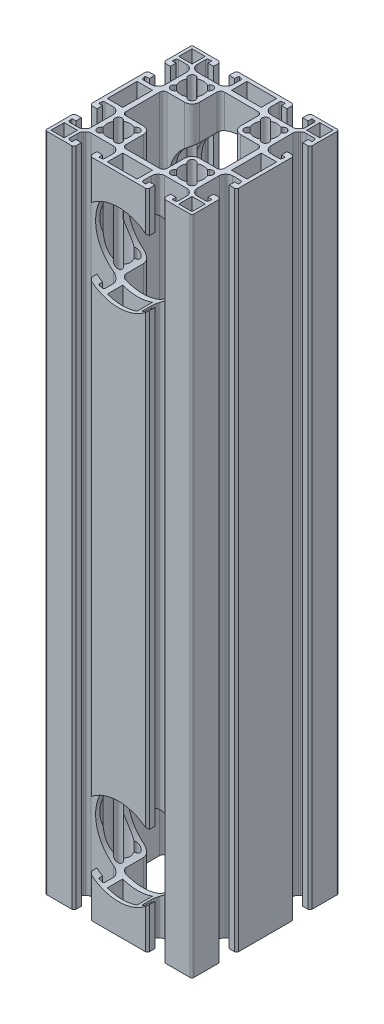
SolidWorks part; units mm, degrees
ref_plane "Front Plane" through (0, 0, 0) normal (0, 0, 1) x (1, 0, 0)
ref_plane "Top Plane" through (0, 0, 0) normal (0, 1, 0) x (1, 0, 0)
ref_plane "Right Plane" through (0, 0, 0) normal (1, 0, 0) x (0, 0, -1)
sketch "Sketch1" plane through (0, 0, 0) normal (0, 1, 0) x (1, 0, 0)
  line L0 (16.5224, 10.1082) -> (17.1083, 10.6941)
  line L2 (14.2799, 13.5226) -> (13.694, 12.9366)
  line L7 (13.694, 19.6541) -> (14.2799, 19.0682)
  line L8 (17.1083, 21.8966) -> (16.5224, 22.4826)
  line L9 (23.2399, 22.4826) -> (22.654, 21.8966)
  line L10 (25.4824, 19.0682) -> (26.0683, 19.6541)
  line L11 (26.0683, 12.9366) -> (25.4824, 13.5226)
  line L12 (22.654, 10.6941) -> (23.2399, 10.1082)
  line L13 (-29.7188, -11.8046) -> (-29.7188, 4.3954)
  line L14 (-38.1188, -11.8046) -> (-29.7188, -11.8046)
  line L15 (-38.1188, 4.3954) -> (-38.1188, -11.8046)
  line L16 (-29.7188, 4.3954) -> (-38.1188, 4.3954)
  line L17 (-23.4776, 10.1082) -> (-22.8917, 10.6941)
  line L18 (-25.7201, 13.5226) -> (-26.306, 12.9366)
  line L19 (-26.306, 19.6541) -> (-25.7201, 19.0682)
  line L20 (-22.8917, 21.8966) -> (-23.4776, 22.4826)
  line L21 (-16.7601, 22.4826) -> (-17.346, 21.8966)
  line L22 (-14.5176, 19.0682) -> (-13.9317, 19.6541)
  line L23 (-13.9317, 12.9366) -> (-14.5176, 13.5226)
  line L24 (-17.346, 10.6941) -> (-16.7601, 10.1082)
  line L26 (23.2399, -17.5174) -> (22.654, -18.1034)
  line L27 (25.4824, -20.9318) -> (26.0683, -20.3459)
  line L28 (26.0683, -27.0634) -> (25.4824, -26.4774)
  line L29 (22.654, -29.3059) -> (23.2399, -29.8918)
  line L30 (16.5224, -29.8918) -> (17.1083, -29.3059)
  line L31 (14.2799, -26.4774) -> (13.694, -27.0634)
  line L32 (13.694, -20.3459) -> (14.2799, -20.9318)
  line L33 (17.1083, -18.1034) -> (16.5224, -17.5174)
  line L41 (-31.3188, -34.9046) -> (-38.5188, -34.9046)
  line L42 (-31.3188, -42.1046) -> (-31.3188, -34.9046)
  line L43 (-38.5188, -42.1046) -> (-31.3188, -42.1046)
  line L44 (-38.5188, -34.9046) -> (-38.5188, -42.1046)
  line L45 (-16.7601, -17.5174) -> (-17.346, -18.1034)
  line L46 (-14.5176, -20.9318) -> (-13.9317, -20.3459)
  line L51 (-13.9317, -27.0634) -> (-14.5176, -26.4774)
  line L52 (-17.346, -29.3059) -> (-16.7601, -29.8918)
  line L53 (-23.4776, -29.8918) -> (-22.8917, -29.3059)
  line L54 (-25.7201, -26.4774) -> (-26.306, -27.0634)
  line L55 (-26.306, -20.3459) -> (-25.7201, -20.9318)
  line L56 (-22.8917, -18.1034) -> (-23.4776, -17.5174)
  line L57 (-38.5188, 27.4954) -> (-31.3188, 27.4954)
  line L58 (-38.5188, 34.6954) -> (-38.5188, 27.4954)
  line L59 (-31.3188, 34.6954) -> (-38.5188, 34.6954)
  line L60 (-31.3188, 27.4954) -> (-31.3188, 34.6954)
  line L61 (38.2812, -34.9046) -> (31.0812, -34.9046)
  line L62 (38.2812, -42.1046) -> (38.2812, -34.9046)
  line L63 (31.0812, -42.1046) -> (38.2812, -42.1046)
  line L64 (31.0812, -34.9046) -> (31.0812, -42.1046)
  line L65 (31.0812, 27.4954) -> (38.2812, 27.4954)
  line L66 (31.0812, 34.6954) -> (31.0812, 27.4954)
  line L67 (38.2812, 34.6954) -> (31.0812, 34.6954)
  line L68 (38.2812, 27.4954) -> (38.2812, 34.6954)
  line L69 (-8.2188, 34.2954) -> (-8.2188, 25.8954)
  line L70 (7.9812, 34.2954) -> (-8.2188, 34.2954)
  line L71 (7.9812, 25.8954) -> (7.9812, 34.2954)
  line L72 (-8.2188, 25.8954) -> (7.9812, 25.8954)
  line L79 (11.0812, -28.5046) -> (11.0812, -18.9046)
  line L80 (-9.3188, -30.5046) -> (9.0812, -30.5046)
  line L81 (-11.3188, -18.9046) -> (-11.3188, -28.5046)
  line L82 (-24.9188, -14.9046) -> (-15.3188, -14.9046)
  line L83 (-26.9188, 5.4954) -> (-26.9188, -12.9046)
  line L84 (-15.3188, 7.4954) -> (-24.9188, 7.4954)
  line L89 (-11.3188, 21.0954) -> (-11.3188, 11.4954)
  line L90 (9.0812, 23.0954) -> (-9.3188, 23.0954)
  line L91 (11.0812, 11.4954) -> (11.0812, 21.0954)
  line L92 (24.6812, 7.4954) -> (15.0812, 7.4954)
  line L93 (26.6812, -12.9046) -> (26.6812, 5.4954)
  line L94 (15.0812, -14.9046) -> (24.6812, -14.9046)
  line L95 (7.9812, -33.3046) -> (-8.2188, -33.3046)
  line L96 (7.9812, -41.7046) -> (7.9812, -33.3046)
  line L97 (-8.2188, -41.7046) -> (7.9812, -41.7046)
  line L98 (-8.2188, -33.3046) -> (-8.2188, -41.7046)
  line L99 (29.4812, 4.3954) -> (29.4812, -11.8046)
  line L100 (37.8812, 4.3954) -> (29.4812, 4.3954)
  line L101 (37.8812, -11.8046) -> (37.8812, 4.3954)
  line L102 (29.4812, -11.8046) -> (37.8812, -11.8046)
  line L103 (39.8812, -42.7046) -> (39.8812, -28.9546)
  line L104 (39.8812, -28.9546) -> (38.8812, -27.9546)
  line L105 (38.8812, -27.9546) -> (35.8812, -27.9546)
  line L106 (35.8812, -27.9546) -> (35.8812, -30.9546)
  line L107 (35.8812, -30.9546) -> (37.4853, -30.9546)
  line L108 (37.9777, -31.5414) -> (37.7979, -32.5609)
  line L109 (36.9116, -33.3046) -> (32.215, -33.3046)
  line L110 (30.0937, -32.4259) -> (29.5598, -31.8921)
  line L111 (28.6812, -29.7708) -> (28.6812, -17.6385)
  line L118 (29.5598, -15.5172) -> (30.0937, -14.9833)
  line L119 (32.215, -14.1046) -> (36.9116, -14.1046)
  line L120 (37.7979, -14.8483) -> (37.9777, -15.8678)
  line L121 (37.4853, -16.4546) -> (35.8812, -16.4546)
  line L122 (35.8812, -16.4546) -> (35.8812, -19.4546)
  line L123 (35.8812, -19.4546) -> (38.8812, -19.4546)
  line L128 (38.8812, -19.4546) -> (39.8812, -18.4546)
  line L129 (39.8812, -18.4546) -> (39.8812, 11.0454)
  line L130 (39.8812, 11.0454) -> (38.8812, 12.0454)
  line L131 (38.8812, 12.0454) -> (35.8812, 12.0454)
  line L132 (35.8812, 12.0454) -> (35.8812, 9.0454)
  line L133 (35.8812, 9.0454) -> (37.4853, 9.0454)
  line L134 (37.9777, 8.4586) -> (37.7979, 7.4391)
  line L135 (36.9116, 6.6954) -> (32.215, 6.6954)
  line L136 (30.0937, 7.5741) -> (29.5598, 8.1079)
  line L137 (28.6812, 10.2292) -> (28.6812, 22.3615)
  line L138 (29.5598, 24.4828) -> (30.0937, 25.0167)
  line L139 (32.215, 25.8954) -> (36.9116, 25.8954)
  line L140 (37.7979, 25.1517) -> (37.9777, 24.1322)
  line L141 (37.4853, 23.5454) -> (35.8812, 23.5454)
  line L142 (35.8812, 23.5454) -> (35.8812, 20.5454)
  line L143 (35.8812, 20.5454) -> (38.8812, 20.5454)
  line L144 (38.8812, 20.5454) -> (39.8812, 21.5454)
  line L145 (39.8812, 21.5454) -> (39.8812, 35.2954)
  line L146 (38.8812, 36.2954) -> (25.1312, 36.2954)
  line L147 (25.1312, 36.2954) -> (24.1312, 35.2954)
  line L148 (24.1312, 35.2954) -> (24.1312, 32.2954)
  line L149 (24.1312, 32.2954) -> (27.1312, 32.2954)
  line L150 (27.1312, 32.2954) -> (27.1312, 33.8995)
  line L157 (27.718, 34.3919) -> (28.7374, 34.2122)
  line L158 (29.4812, 33.3258) -> (29.4812, 28.6292)
  line L159 (28.6025, 26.5079) -> (28.0686, 25.9741)
  line L160 (25.9473, 25.0954) -> (13.815, 25.0954)
  line L161 (11.6937, 25.9741) -> (11.1598, 26.5079)
  line L162 (10.2812, 28.6292) -> (10.2812, 33.3258)
  line L167 (11.0249, 34.2122) -> (12.0443, 34.3919)
  line L172 (12.6312, 33.8995) -> (12.6312, 32.2954)
  line L173 (12.6312, 32.2954) -> (15.6312, 32.2954)
  line L178 (15.6312, 32.2954) -> (15.6312, 35.2954)
  line L179 (15.6312, 35.2954) -> (14.6312, 36.2954)
  line L183 (14.6312, 36.2954) -> (-14.8688, 36.2954)
  line L184 (-14.8688, 36.2954) -> (-15.8688, 35.2954)
  line L189 (-15.8688, 35.2954) -> (-15.8688, 32.2954)
  line L190 (-15.8688, 32.2954) -> (-12.8688, 32.2954)
  line L195 (-12.8688, 32.2954) -> (-12.8688, 33.8995)
  line L196 (-12.282, 34.3919) -> (-11.2626, 34.2122)
  line L198 (-10.5188, 33.3258) -> (-10.5188, 28.6292)
  line L199 (-11.3975, 26.5079) -> (-11.9314, 25.9741)
  line L200 (-14.0527, 25.0954) -> (-26.185, 25.0954)
  line L201 (-28.3063, 25.9741) -> (-28.8402, 26.5079)
  line L202 (-29.7188, 28.6292) -> (-29.7188, 33.3258)
  line L203 (-28.9751, 34.2122) -> (-27.9557, 34.3919)
  line L204 (-27.3688, 33.8995) -> (-27.3688, 32.2954)
  line L205 (-27.3688, 32.2954) -> (-24.3688, 32.2954)
  line L206 (-24.3688, 32.2954) -> (-24.3688, 35.2954)
  line L207 (-24.3688, 35.2954) -> (-25.3688, 36.2954)
  line L208 (-25.3688, 36.2954) -> (-39.1188, 36.2954)
  line L209 (-40.1188, 35.2954) -> (-40.1188, 21.5454)
  line L210 (-40.1188, 21.5454) -> (-39.1188, 20.5454)
  line L211 (-39.1188, 20.5454) -> (-36.1188, 20.5454)
  line L212 (-36.1188, 20.5454) -> (-36.1188, 23.5454)
  line L213 (-36.1188, 23.5454) -> (-37.723, 23.5454)
  line L214 (-38.2154, 24.1322) -> (-38.0356, 25.1517)
  line L215 (-37.1493, 25.8954) -> (-32.4527, 25.8954)
  line L216 (-30.3314, 25.0167) -> (-29.7975, 24.4828)
  line L217 (-28.9188, 22.3615) -> (-28.9188, 10.2292)
  line L218 (-29.7975, 8.1079) -> (-30.3314, 7.5741)
  line L219 (-32.4527, 6.6954) -> (-37.1493, 6.6954)
  line L220 (-38.0356, 7.4391) -> (-38.2154, 8.4586)
  line L221 (-37.723, 9.0454) -> (-36.1188, 9.0454)
  line L222 (-36.1188, 9.0454) -> (-36.1188, 12.0454)
  line L223 (-36.1188, 12.0454) -> (-39.1188, 12.0454)
  line L224 (-39.1188, 12.0454) -> (-40.1188, 11.0454)
  line L225 (-40.1188, 11.0454) -> (-40.1188, -18.4546)
  line L226 (-40.1188, -18.4546) -> (-39.1188, -19.4546)
  line L227 (-39.1188, -19.4546) -> (-36.1188, -19.4546)
  line L228 (-36.1188, -19.4546) -> (-36.1188, -16.4546)
  line L229 (-36.1188, -16.4546) -> (-37.723, -16.4546)
  line L230 (-38.2154, -15.8678) -> (-38.0356, -14.8483)
  line L231 (-37.1493, -14.1046) -> (-32.4527, -14.1046)
  line L232 (-30.3314, -14.9833) -> (-29.7975, -15.5172)
  line L233 (-28.9188, -17.6385) -> (-28.9188, -29.7708)
  line L234 (-29.7975, -31.8921) -> (-30.3314, -32.4259)
  line L235 (-32.4527, -33.3046) -> (-37.1493, -33.3046)
  line L236 (-38.0356, -32.5609) -> (-38.2154, -31.5414)
  line L237 (-37.723, -30.9546) -> (-36.1188, -30.9546)
  line L238 (-36.1188, -30.9546) -> (-36.1188, -27.9546)
  line L239 (-36.1188, -27.9546) -> (-39.1188, -27.9546)
  line L240 (-39.1188, -27.9546) -> (-40.1188, -28.9546)
  line L241 (-40.1188, -28.9546) -> (-40.1188, -42.7046)
  line L242 (-39.1188, -43.7046) -> (-25.3688, -43.7046)
  line L243 (-25.3688, -43.7046) -> (-24.3688, -42.7046)
  line L244 (-24.3688, -42.7046) -> (-24.3688, -39.7046)
  line L245 (-24.3688, -39.7046) -> (-27.3688, -39.7046)
  line L246 (-27.3688, -39.7046) -> (-27.3688, -41.3087)
  line L247 (-27.9557, -41.8011) -> (-28.9751, -41.6214)
  line L248 (-29.7188, -40.7351) -> (-29.7188, -36.0385)
  line L249 (-28.8402, -33.9172) -> (-28.3063, -33.3833)
  line L250 (-26.185, -32.5046) -> (-14.0527, -32.5046)
  line L251 (-11.9314, -33.3833) -> (-11.3975, -33.9172)
  line L252 (-10.5188, -36.0385) -> (-10.5188, -40.7351)
  line L253 (-11.2626, -41.6214) -> (-12.282, -41.8011)
  line L254 (-12.8688, -41.3087) -> (-12.8688, -39.7046)
  line L255 (-12.8688, -39.7046) -> (-15.8688, -39.7046)
  line L256 (-15.8688, -39.7046) -> (-15.8688, -42.7046)
  line L257 (-15.8688, -42.7046) -> (-14.8688, -43.7046)
  line L258 (-14.8688, -43.7046) -> (14.6312, -43.7046)
  line L259 (14.6312, -43.7046) -> (15.6312, -42.7046)
  line L260 (15.6312, -42.7046) -> (15.6312, -39.7046)
  line L261 (15.6312, -39.7046) -> (12.6312, -39.7046)
  line L262 (12.6312, -39.7046) -> (12.6312, -41.3087)
  line L263 (12.0443, -41.8011) -> (11.0249, -41.6214)
  line L264 (10.2812, -40.7351) -> (10.2812, -36.0385)
  line L265 (11.1598, -33.9172) -> (11.6937, -33.3833)
  line L266 (13.815, -32.5046) -> (25.9473, -32.5046)
  line L267 (28.0686, -33.3833) -> (28.6025, -33.9172)
  line L268 (29.4812, -36.0385) -> (29.4812, -40.7351)
  line L269 (28.7374, -41.6214) -> (27.718, -41.8011)
  line L270 (27.1312, -41.3087) -> (27.1312, -39.7046)
  line L271 (27.1312, -39.7046) -> (24.1312, -39.7046)
  line L272 (24.1312, -39.7046) -> (24.1312, -42.7046)
  line L273 (24.1312, -42.7046) -> (25.1312, -43.7046)
  line L274 (25.1312, -43.7046) -> (38.8812, -43.7046)
  arc A0 (17.1083, 10.6941) -> (22.654, 10.6941) centre (19.8812, 16.2954) ccw
  arc A1 (13.694, 12.9366) -> (16.5224, 10.1082) centre (15.1082, 11.5224) ccw
  arc A2 (14.2799, 19.0682) -> (14.2799, 13.5226) centre (19.8812, 16.2954) ccw
  arc A3 (16.5224, 22.4826) -> (13.694, 19.6541) centre (15.1082, 21.0684) ccw
  arc A4 (22.654, 21.8966) -> (17.1083, 21.8966) centre (19.8812, 16.2954) ccw
  arc A5 (26.0683, 19.6541) -> (23.2399, 22.4826) centre (24.6541, 21.0684) ccw
  arc A6 (25.4824, 13.5226) -> (25.4824, 19.0682) centre (19.8812, 16.2954) ccw
  arc A7 (23.2399, 10.1082) -> (26.0683, 12.9366) centre (24.6541, 11.5224) ccw
  arc A8 (-22.8917, 10.6941) -> (-17.346, 10.6941) centre (-20.1188, 16.2954) ccw
  arc A9 (-26.306, 12.9366) -> (-23.4776, 10.1082) centre (-24.8918, 11.5224) ccw
  arc A10 (-25.7201, 19.0682) -> (-25.7201, 13.5226) centre (-20.1188, 16.2954) ccw
  arc A11 (-23.4776, 22.4826) -> (-26.306, 19.6541) centre (-24.8918, 21.0684) ccw
  arc A12 (-17.346, 21.8966) -> (-22.8917, 21.8966) centre (-20.1188, 16.2954) ccw
  arc A13 (-13.9317, 19.6541) -> (-16.7601, 22.4826) centre (-15.3459, 21.0684) ccw
  arc A14 (-14.5176, 13.5226) -> (-14.5176, 19.0682) centre (-20.1188, 16.2954) ccw
  arc A15 (-16.7601, 10.1082) -> (-13.9317, 12.9366) centre (-15.3459, 11.5224) ccw
  arc A50 (22.654, -18.1034) -> (17.1083, -18.1034) centre (19.8812, -23.7046) ccw
  arc A51 (26.0683, -20.3459) -> (23.2399, -17.5174) centre (24.6541, -18.9316) ccw
  arc A52 (25.4824, -26.4774) -> (25.4824, -20.9318) centre (19.8812, -23.7046) ccw
  arc A53 (23.2399, -29.8918) -> (26.0683, -27.0634) centre (24.6541, -28.4776) ccw
  arc A54 (17.1083, -29.3059) -> (22.654, -29.3059) centre (19.8812, -23.7046) ccw
  arc A55 (13.694, -27.0634) -> (16.5224, -29.8918) centre (15.1082, -28.4776) ccw
  arc A56 (14.2799, -20.9318) -> (14.2799, -26.4774) centre (19.8812, -23.7046) ccw
  arc A57 (16.5224, -17.5174) -> (13.694, -20.3459) centre (15.1082, -18.9316) ccw
  arc A58 (-17.346, -18.1034) -> (-22.8917, -18.1034) centre (-20.1188, -23.7046) ccw
  arc A59 (-13.9317, -20.3459) -> (-16.7601, -17.5174) centre (-15.3459, -18.9316) ccw
  arc A60 (-14.5176, -26.4774) -> (-14.5176, -20.9318) centre (-20.1188, -23.7046) ccw
  arc A61 (-16.7601, -29.8918) -> (-13.9317, -27.0634) centre (-15.3459, -28.4776) ccw
  arc A62 (-22.8917, -29.3059) -> (-17.346, -29.3059) centre (-20.1188, -23.7046) ccw
  arc A63 (-26.306, -27.0634) -> (-23.4776, -29.8918) centre (-24.8918, -28.4776) ccw
  arc A64 (-25.7201, -20.9318) -> (-25.7201, -26.4774) centre (-20.1188, -23.7046) ccw
  arc A65 (-23.4776, -17.5174) -> (-26.306, -20.3459) centre (-24.8918, -18.9316) ccw
  arc A66 (15.0812, -14.9046) -> (11.0812, -18.9046) centre (15.0812, -18.9046) ccw
  arc A67 (9.0812, -30.5046) -> (11.0812, -28.5046) centre (9.0812, -28.5046) ccw
  arc A68 (-11.3188, -28.5046) -> (-9.3188, -30.5046) centre (-9.3188, -28.5046) ccw
  arc A69 (-11.3188, -18.9046) -> (-15.3188, -14.9046) centre (-15.3188, -18.9046) ccw
  arc A70 (-26.9188, -12.9046) -> (-24.9188, -14.9046) centre (-24.9188, -12.9046) ccw
  arc A71 (-24.9188, 7.4954) -> (-26.9188, 5.4954) centre (-24.9188, 5.4954) ccw
  arc A72 (-15.3188, 7.4954) -> (-11.3188, 11.4954) centre (-15.3188, 11.4954) ccw
  arc A73 (-9.3188, 23.0954) -> (-11.3188, 21.0954) centre (-9.3188, 21.0954) ccw
  arc A74 (11.0812, 21.0954) -> (9.0812, 23.0954) centre (9.0812, 21.0954) ccw
  arc A75 (11.0812, 11.4954) -> (15.0812, 7.4954) centre (15.0812, 11.4954) ccw
  arc A76 (26.6812, 5.4954) -> (24.6812, 7.4954) centre (24.6812, 5.4954) ccw
  arc A77 (24.6812, -14.9046) -> (26.6812, -12.9046) centre (24.6812, -12.9046) ccw
  arc A78 (38.8812, -43.7046) -> (39.8812, -42.7046) centre (38.8812, -42.7046) ccw
  arc A79 (37.9777, -31.5414) -> (37.4853, -30.9546) centre (37.4853, -31.4546) ccw
  arc A80 (36.9116, -33.3046) -> (37.7979, -32.5609) centre (36.9116, -32.4046) ccw
  arc A81 (30.0937, -32.4259) -> (32.215, -33.3046) centre (32.215, -30.3046) ccw
  arc A82 (28.6812, -29.7708) -> (29.5598, -31.8921) centre (31.6812, -29.7708) ccw
  arc A83 (29.5598, -15.5172) -> (28.6812, -17.6385) centre (31.6812, -17.6385) ccw
  arc A84 (32.215, -14.1046) -> (30.0937, -14.9833) centre (32.215, -17.1046) ccw
  arc A85 (37.7979, -14.8483) -> (36.9116, -14.1046) centre (36.9116, -15.0046) ccw
  arc A86 (37.4853, -16.4546) -> (37.9777, -15.8678) centre (37.4853, -15.9546) ccw
  arc A87 (37.9777, 8.4586) -> (37.4853, 9.0454) centre (37.4853, 8.5454) ccw
  arc A88 (36.9116, 6.6954) -> (37.7979, 7.4391) centre (36.9116, 7.5954) ccw
  arc A89 (30.0937, 7.5741) -> (32.215, 6.6954) centre (32.215, 9.6954) ccw
  arc A90 (28.6812, 10.2292) -> (29.5598, 8.1079) centre (31.6812, 10.2292) ccw
  arc A91 (29.5598, 24.4828) -> (28.6812, 22.3615) centre (31.6812, 22.3615) ccw
  arc A92 (32.215, 25.8954) -> (30.0937, 25.0167) centre (32.215, 22.8954) ccw
  arc A93 (37.7979, 25.1517) -> (36.9116, 25.8954) centre (36.9116, 24.9954) ccw
  arc A94 (37.4853, 23.5454) -> (37.9777, 24.1322) centre (37.4853, 24.0454) ccw
  arc A95 (39.8812, 35.2954) -> (38.8812, 36.2954) centre (38.8812, 35.2954) ccw
  arc A96 (27.718, 34.3919) -> (27.1312, 33.8995) centre (27.6312, 33.8995) ccw
  arc A97 (29.4812, 33.3258) -> (28.7374, 34.2122) centre (28.5812, 33.3258) ccw
  arc A98 (28.6025, 26.5079) -> (29.4812, 28.6292) centre (26.4812, 28.6292) ccw
  arc A99 (25.9473, 25.0954) -> (28.0686, 25.9741) centre (25.9473, 28.0954) ccw
  arc A100 (11.6937, 25.9741) -> (13.815, 25.0954) centre (13.815, 28.0954) ccw
  arc A101 (10.2812, 28.6292) -> (11.1598, 26.5079) centre (13.2812, 28.6292) ccw
  arc A102 (11.0249, 34.2122) -> (10.2812, 33.3258) centre (11.1812, 33.3258) ccw
  arc A103 (12.6312, 33.8995) -> (12.0443, 34.3919) centre (12.1312, 33.8995) ccw
  arc A104 (-12.282, 34.3919) -> (-12.8688, 33.8995) centre (-12.3688, 33.8995) ccw
  arc A105 (-10.5188, 33.3258) -> (-11.2626, 34.2122) centre (-11.4188, 33.3258) ccw
  arc A106 (-11.3975, 26.5079) -> (-10.5188, 28.6292) centre (-13.5188, 28.6292) ccw
  arc A107 (-14.0527, 25.0954) -> (-11.9314, 25.9741) centre (-14.0527, 28.0954) ccw
  arc A108 (-28.3063, 25.9741) -> (-26.185, 25.0954) centre (-26.185, 28.0954) ccw
  arc A109 (-29.7188, 28.6292) -> (-28.8402, 26.5079) centre (-26.7188, 28.6292) ccw
  arc A110 (-28.9751, 34.2122) -> (-29.7188, 33.3258) centre (-28.8188, 33.3258) ccw
  arc A111 (-27.3688, 33.8995) -> (-27.9557, 34.3919) centre (-27.8688, 33.8995) ccw
  arc A112 (-39.1188, 36.2954) -> (-40.1188, 35.2954) centre (-39.1188, 35.2954) ccw
  arc A113 (-38.2154, 24.1322) -> (-37.723, 23.5454) centre (-37.723, 24.0454) ccw
  arc A114 (-37.1493, 25.8954) -> (-38.0356, 25.1517) centre (-37.1493, 24.9954) ccw
  arc A115 (-30.3314, 25.0167) -> (-32.4527, 25.8954) centre (-32.4527, 22.8954) ccw
  arc A116 (-28.9188, 22.3615) -> (-29.7975, 24.4828) centre (-31.9188, 22.3615) ccw
  arc A117 (-29.7975, 8.1079) -> (-28.9188, 10.2292) centre (-31.9188, 10.2292) ccw
  arc A118 (-32.4527, 6.6954) -> (-30.3314, 7.5741) centre (-32.4527, 9.6954) ccw
  arc A119 (-38.0356, 7.4391) -> (-37.1493, 6.6954) centre (-37.1493, 7.5954) ccw
  arc A120 (-37.723, 9.0454) -> (-38.2154, 8.4586) centre (-37.723, 8.5454) ccw
  arc A121 (-38.2154, -15.8678) -> (-37.723, -16.4546) centre (-37.723, -15.9546) ccw
  arc A122 (-37.1493, -14.1046) -> (-38.0356, -14.8483) centre (-37.1493, -15.0046) ccw
  arc A123 (-30.3314, -14.9833) -> (-32.4527, -14.1046) centre (-32.4527, -17.1046) ccw
  arc A124 (-28.9188, -17.6385) -> (-29.7975, -15.5172) centre (-31.9188, -17.6385) ccw
  arc A125 (-29.7975, -31.8921) -> (-28.9188, -29.7708) centre (-31.9188, -29.7708) ccw
  arc A126 (-32.4527, -33.3046) -> (-30.3314, -32.4259) centre (-32.4527, -30.3046) ccw
  arc A127 (-38.0356, -32.5609) -> (-37.1493, -33.3046) centre (-37.1493, -32.4046) ccw
  arc A128 (-37.723, -30.9546) -> (-38.2154, -31.5414) centre (-37.723, -31.4546) ccw
  arc A129 (-40.1188, -42.7046) -> (-39.1188, -43.7046) centre (-39.1188, -42.7046) ccw
  arc A130 (-27.9557, -41.8011) -> (-27.3688, -41.3087) centre (-27.8688, -41.3087) ccw
  arc A131 (-29.7188, -40.7351) -> (-28.9751, -41.6214) centre (-28.8188, -40.7351) ccw
  arc A132 (-28.8402, -33.9172) -> (-29.7188, -36.0385) centre (-26.7188, -36.0385) ccw
  arc A133 (-26.185, -32.5046) -> (-28.3063, -33.3833) centre (-26.185, -35.5046) ccw
  arc A134 (-11.9314, -33.3833) -> (-14.0527, -32.5046) centre (-14.0527, -35.5046) ccw
  arc A135 (-10.5188, -36.0385) -> (-11.3975, -33.9172) centre (-13.5188, -36.0385) ccw
  arc A136 (-11.2626, -41.6214) -> (-10.5188, -40.7351) centre (-11.4188, -40.7351) ccw
  arc A137 (-12.8688, -41.3087) -> (-12.282, -41.8011) centre (-12.3688, -41.3087) ccw
  arc A138 (12.0443, -41.8011) -> (12.6312, -41.3087) centre (12.1312, -41.3087) ccw
  arc A139 (10.2812, -40.7351) -> (11.0249, -41.6214) centre (11.1812, -40.7351) ccw
  arc A140 (11.1598, -33.9172) -> (10.2812, -36.0385) centre (13.2812, -36.0385) ccw
  arc A141 (13.815, -32.5046) -> (11.6937, -33.3833) centre (13.815, -35.5046) ccw
  arc A142 (28.0686, -33.3833) -> (25.9473, -32.5046) centre (25.9473, -35.5046) ccw
  arc A143 (29.4812, -36.0385) -> (28.6025, -33.9172) centre (26.4812, -36.0385) ccw
  arc A144 (28.7374, -41.6214) -> (29.4812, -40.7351) centre (28.5812, -40.7351) ccw
  arc A145 (27.1312, -41.3087) -> (27.718, -41.8011) centre (27.6312, -41.3087) ccw
extrude "Boss-Extrude1" add sketch "Sketch1" along normal blind 360
sketch "Sketch2" plane through (0, 0, -36.2954) normal (0, 0, -1) x (-1, 0, 0)
  line L0 (0.1188, 360) -> (0.1188, 0) construction
  line L1 (-14.6312, 360) -> (14.8688, 360) construction
  line L2 (-14.6312, 0) -> (14.8688, 0) construction
  line L3 (-38.8812, 180) -> (39.1188, 180) construction
  line L4 (-38.8812, 360) -> (-38.8812, 0) construction
  line L5 (39.1188, 360) -> (39.1188, 0) construction
  circle A0 centre (0.1188, 320) radius 23.7
  circle A1 centre (0.1188, 40) radius 23.7
  dimension "D1" = 47.4
  dimension "D2" = 40
extrude "Cut-Extrude1" cut sketch "Sketch2" against normal through all
